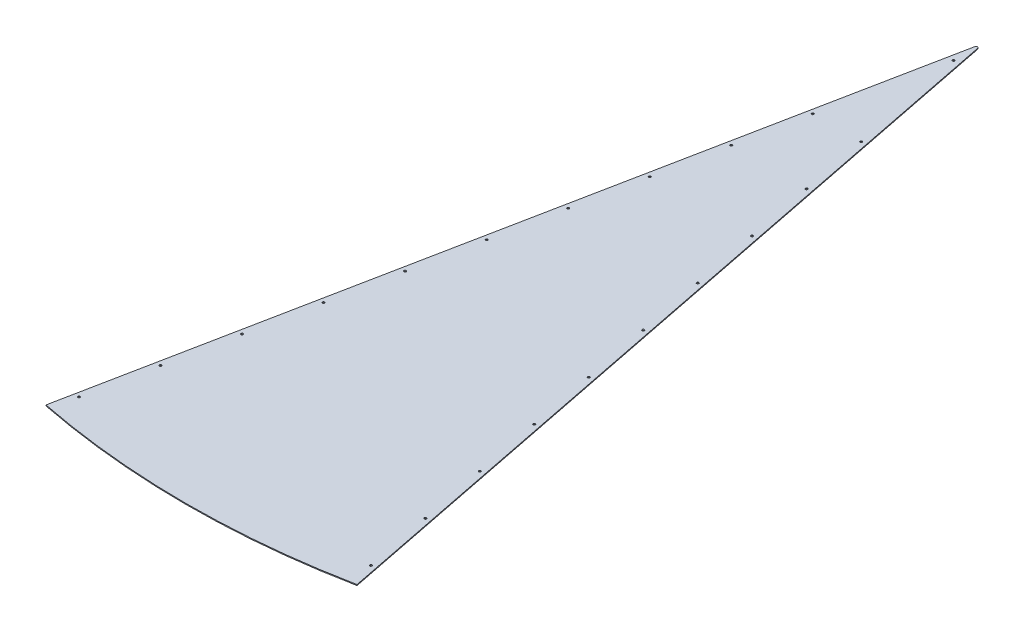
SolidWorks part; units mm, degrees
ref_plane "Front Plane" through (0, 0, 0) normal (0, 0, 1) x (1, 0, 0)
ref_plane "Top Plane" through (0, 0, 0) normal (0, 1, 0) x (1, 0, 0)
ref_plane "Right Plane" through (0, 0, 0) normal (1, 0, 0) x (0, 0, -1)
sketch "Sketch1" plane through (0, 0, 0) normal (0, 1, 0) x (1, 0, 0)
  line L0 (0, 0) -> (0, -20) construction
  line L1 (-3.769, -18.9483) -> (-419.4442, -2108.6884)
  line L2 (3.769, -18.9483) -> (419.4442, -2108.6884)
  line L3 (-3.769, -18.9483) -> (0, 0) construction
  line L4 (0, 0) -> (3.769, -18.9483) construction
  arc A0 (-419.4442, -2108.6884) -> (419.4442, -2108.6884) centre (0, 0) ccw
  arc A1 (-3.769, -18.9483) -> (3.769, -18.9483) centre (0, -20) cw
  dimension "D3" = 20
  dimension "D1" = 22.5
  dimension "D2" = 2150
extrude "Boss-Extrude1" add sketch "Sketch1" along normal blind 2.5
sketch "Sketch2" plane through (0, 2.5, 0) normal (0, 1, 0) x (1, 0, 0)
  line L1 (-419.4442, -2108.6884) -> (-423.7021, -2107.8414) construction
  line L2 (8.9812, -21.4844) -> (-406.694, -2111.2245)
  line L3 (8.9812, -21.4844) -> (-406.694, -2111.2245) construction
  line L4 (-393.6229, -2045.5119) -> (-357.141, -1862.1051) construction
  line L5 (0, 0) -> (0, -119.352) construction
  circle A0 centre (-393.6229, -2045.5119) radius 3
  circle A1 centre (-357.141, -1862.1051) radius 3
  circle A2 centre (-320.6592, -1678.6982) radius 3
  circle A3 centre (-284.1773, -1495.2914) radius 3
  circle A4 centre (-247.6954, -1311.8845) radius 3
  circle A5 centre (-211.2135, -1128.4777) radius 3
  circle A6 centre (-174.7316, -945.0708) radius 3
  circle A7 centre (-138.2497, -761.664) radius 3
  circle A8 centre (-101.7678, -578.2571) radius 3
  circle A9 centre (-65.2859, -394.8503) radius 3
  circle A10 centre (65.2859, -394.8503) radius 3
  circle A11 centre (101.7678, -578.2571) radius 3
  circle A12 centre (138.2497, -761.664) radius 3
  circle A13 centre (174.7316, -945.0708) radius 3
  circle A14 centre (211.2135, -1128.4777) radius 3
  circle A15 centre (247.6954, -1311.8845) radius 3
  circle A16 centre (284.1773, -1495.2914) radius 3
  circle A17 centre (320.6592, -1678.6982) radius 3
  circle A18 centre (357.141, -1862.1051) radius 3
  circle A19 centre (393.6229, -2045.5119) radius 3
  circle A20 centre (0, -80) radius 3
  dimension "D2" = 6
  dimension "D6" = 6
  dimension "D3" = 67
  dimension "D5" = 187
  dimension "D7" = 80
  dimension "D1" = 13
  dimension "D4" = 10
extrude "Cut-Extrude1" cut sketch "Sketch2" against normal up to surface (2.5 mm away) up to face at (0, 0, 1073.4309)
ref_axis "Axis1" through (0, 0, 0) along (0, 1, 0)
